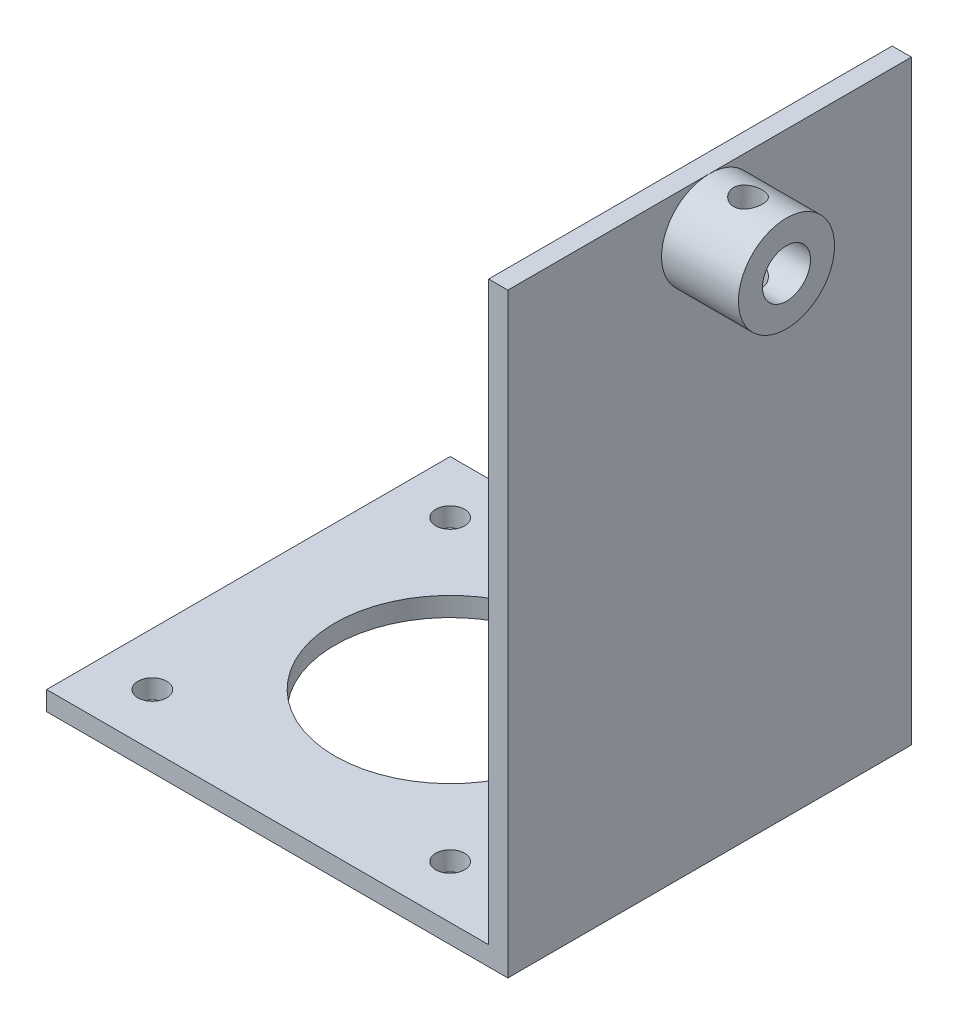
SolidWorks part; units mm, degrees
material "5052-H36"
ref_plane "前视基准面" through (0, 0, 0) normal (0, 0, 1) x (1, 0, 0)
ref_plane "上视基准面" through (0, 0, 0) normal (0, 1, 0) x (1, 0, 0)
ref_plane "右视基准面" through (0, 0, 0) normal (1, 0, 0) x (0, 0, -1)
sketch "草图1" plane through (0, 0, 0) normal (0, 1, 0) x (1, 0, 0)
  line L1 (0, 0) -> (48, 0)
  line L2 (0, 0) -> (0, 42)
  line L3 (0, 42) -> (48, 42)
  line L4 (48, 0) -> (48, 42)
extrude "凸台-拉伸1" add sketch "草图1" along normal blind 2
sketch "草图2" plane through (0, 2, 0) normal (0, 1, 0) x (1, 0, 0)
  circle A0 centre (21, 21) radius 12
  circle A1 centre (36.5, 36.5) radius 1.5
  circle A2 centre (36.5, 5.5) radius 1.5
  circle A3 centre (5.5, 5.5) radius 1.5
  circle A4 centre (5.5, 36.5) radius 1.5
extrude "切除-拉伸1" cut sketch "草图2" against normal blind 2
sketch "草图9" plane through (0, 2, 0) normal (0, 1, 0) x (1, 0, 0)
  line L0 (48, 42) -> (48, 0)
  line L1 (48, 0) -> (46, 0)
  line L2 (0, 0) -> (48, 0) construction
  line L3 (46, 0) -> (46, 42)
  line L4 (48, 42) -> (0, 42) construction
  line L5 (46, 42) -> (48, 42)
extrude "凸台-拉伸7" add sketch "草图9" along normal blind 60
sketch "草图10" plane through (48, 0, 0) normal (1, 0, 0) x (0, 0, -1)
  line L0 (21, 62) -> (21, 57)
  line L1 (0, 62) -> (42, 62) construction
  circle A0 centre (21, 57) radius 5
extrude "凸台-拉伸9" add sketch "草图10" along normal blind 8 contours A0 region at (48, 53.5645, -17.5645)
sketch "草图11" plane through (56, 0, 0) normal (1, 0, 0) x (0, 0, -1)
  circle A0 centre (21, 57) radius 2.5
extrude "切除-拉伸4" cut sketch "草图11" against normal blind 10
sketch "草图12" plane through (0, 0, 0) normal (0, 1, 0) x (1, 0, 0)
  line L0 (48, 21) -> (52, 21)
  line L1 (48, 16) -> (48, 26) construction
  circle A0 centre (52, 21) radius 1.5
extrude "切除-拉伸6" cut sketch "草图12" along normal through all contours A0
